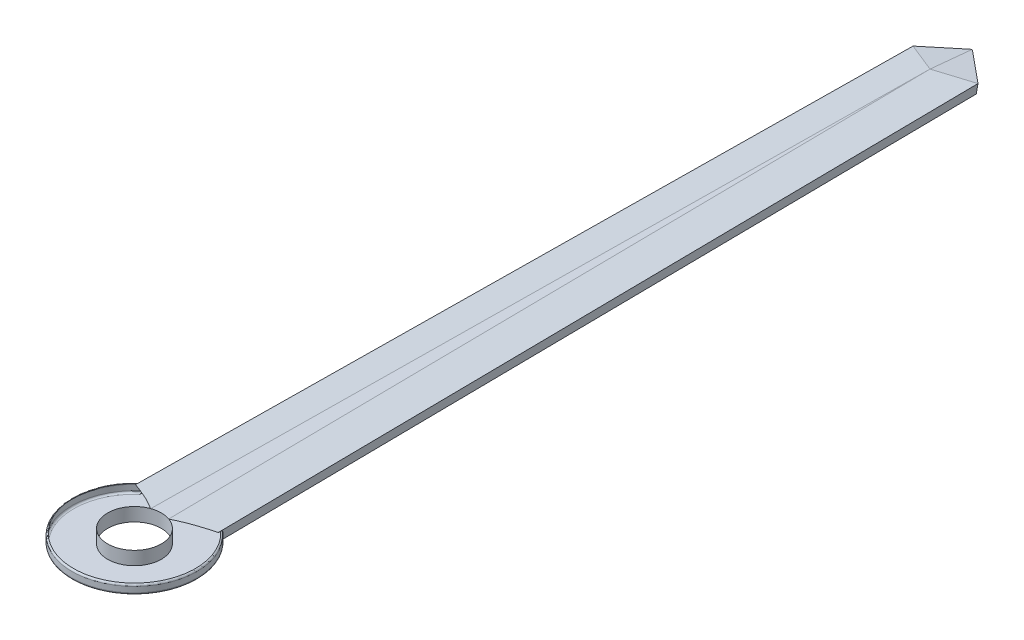
SolidWorks part; units mm, degrees
ref_plane "Front Plane" through (0, 0, 0) normal (0, 0, 1) x (1, 0, 0)
ref_plane "Top Plane" through (0, 0, 0) normal (0, 1, 0) x (1, 0, 0)
ref_plane "Right Plane" through (0, 0, 0) normal (1, 0, 0) x (0, 0, -1)
sketch "Sketch1" plane through (0, 0, 0) normal (0, 1, 0) x (1, 0, 0)
  line L0 (-0.635, 0.6222) -> (-0.508, 11.5442)
  line L1 (-0.508, 11.5442) -> (0, 11.9634)
  line L2 (0, 11.9634) -> (0.508, 11.5442)
  line L6 (0.508, 11.5442) -> (0.635, 0.6222)
  circle A0 centre (0, 0) radius 0.381
  arc A1 (-0.635, 0.6222) -> (0.635, 0.6222) centre (0, 0) ccw
  dimension "D1" = 0.762
  dimension "D2" = 1.778
  dimension "D3" = 1.27
extrude "Extrude1" add sketch "Sketch1" along normal blind 0.1905
chamfer "Chamfer1" distance 0.0635 angle 82.91 8 edges at (0.5715, 0, -6.0832) (0.254, 0, -11.7538) (-0.254, 0, -11.7538) (-0.5715, 0, -6.0832) (0.5715, 0.1905, -6.0832) (0.254, 0.1905, -11.7538) (-0.254, 0.1905, -11.7538) (-0.5715, 0.1905, -6.0832)
chamfer "Chamfer2" distance 0.0635 angle 82.91 1 edges at (0, 0.1905, 0.889)
fillet "Fillet1" radius 0.0254 3 edges at (0, 0.0664, -11.8918) (0, 0.127, 0.889) (0, 0, 0.889)
